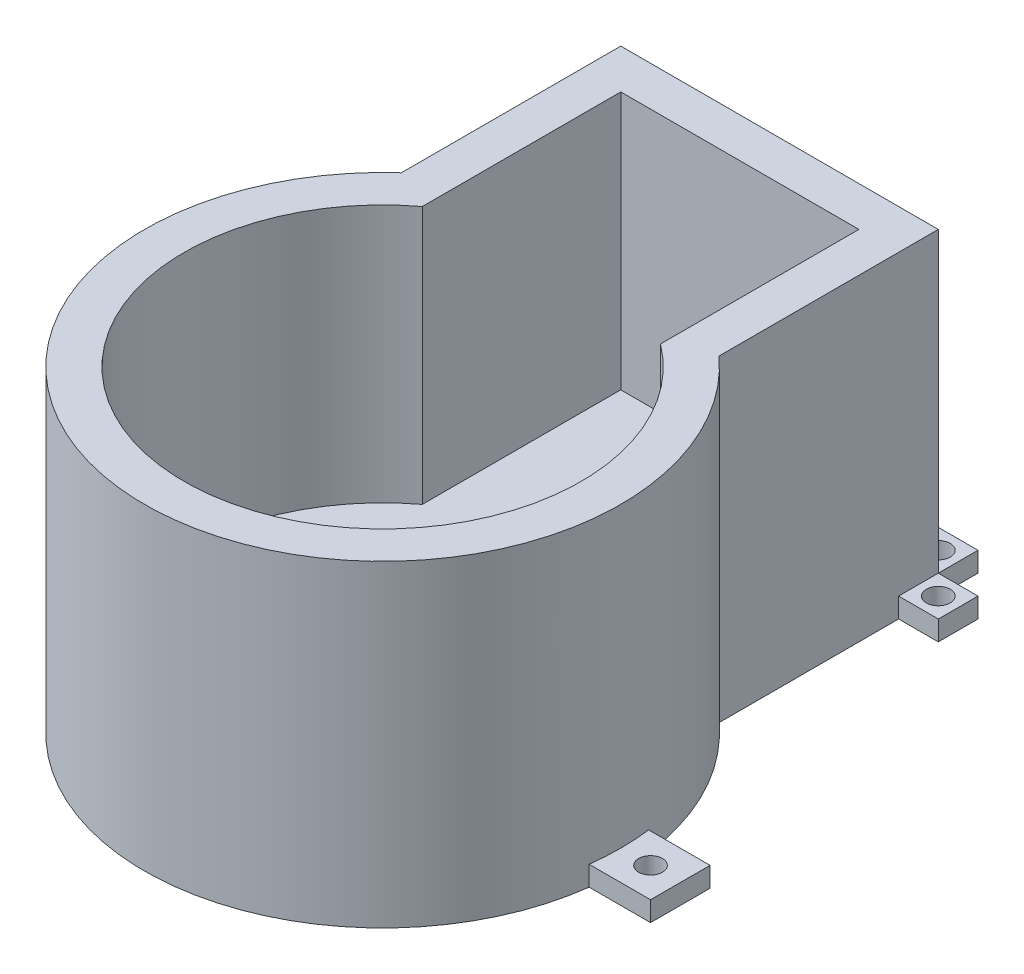
SolidWorks part; units mm, degrees
ref_plane "Front Plane" through (0, 0, 0) normal (0, 0, 1) x (1, 0, 0)
ref_plane "Top Plane" through (0, 0, 0) normal (0, 1, 0) x (1, 0, 0)
ref_plane "Right Plane" through (0, 0, 0) normal (1, 0, 0) x (0, 0, -1)
sketch "Sketch1" plane through (0, 0, 0) normal (0, 1, 0) x (1, 0, 0)
  line L0 (0, 40) -> (0, -40) construction
  line L1 (-40, 40) -> (40, 40)
  line L2 (-40, 40) -> (-40, -40)
  line L3 (-40, -40) -> (40, -40)
  line L4 (40, 40) -> (40, -40)
  line L5 (-40, 40) -> (40, -40) construction
  line L6 (-40, -40) -> (40, 40) construction
  circle A0 centre (0, -60) radius 60
  point P0 (0, 0)
  dimension "D4" = 120
  dimension "D1" = 80
  dimension "D2" = 80
  dimension "D3" = 60
extrude "Boss-Extrude1" add sketch "Sketch1" along normal blind 80
sketch "Sketch2" plane through (0, 80, 0) normal (0, 1, 0) x (1, 0, 0)
  line L1 (-30, 30) -> (30, 30)
  line L2 (-30, 30) -> (-30, -30)
  line L3 (-30, -30) -> (30, -30)
  line L4 (30, 30) -> (30, -30)
  line L5 (-30, 30) -> (30, -30) construction
  line L6 (-30, -30) -> (30, 30) construction
  circle A0 centre (0, -60) radius 50
  point P0 (0, 0)
  dimension "D3" = 100
  dimension "D1" = 60
  dimension "D2" = 60
extrude "Cut-Extrude1" cut sketch "Sketch2" against normal blind 65 contours A0 L4 L1 L2 | L4 A0 L2 L3 | L2 A0 L4 L3 region at (0, 80, -8.3069) region at (0, 80, 21.3384) region at (0, 80, 65.6974)
sketch "Sketch3" plane through (0, 0, 0) normal (0, -1, 0) x (1, 0, 0)
  line L0 (0, 120) -> (0, -40) construction
  line L1 (30, -30) -> (50, -30)
  line L2 (30, -30) -> (30, -50)
  line L3 (30, -50) -> (50, -50)
  line L4 (50, -30) -> (50, -50)
  line L5 (30, -30) -> (50, -50) construction
  line L6 (30, -50) -> (50, -30) construction
  line L7 (-40, -40) -> (40, -40) construction
  line L8 (-30, -50) -> (-50, -30) construction
  line L9 (50, -50) -> (40, -50)
  line L10 (50, -50) -> (50, -40)
  line L11 (50, -40) -> (40, -40)
  line L12 (40, -50) -> (40, -40)
  line L13 (-30, -30) -> (-50, -50) construction
  line L14 (-40, -50) -> (-40, -40)
  line L15 (-50, -40) -> (-40, -40)
  line L16 (-50, -50) -> (-50, -40)
  line L17 (-50, -50) -> (-40, -50)
  line L18 (-50, -30) -> (-50, -50)
  line L19 (-30, -50) -> (-50, -50)
  line L20 (-30, -30) -> (-30, -50)
  line L21 (-30, -30) -> (-50, -30)
  line L22 (-60, 60) -> (60, 60) construction
  line L23 (-60, 60) -> (-75, 60) construction
  line L24 (-75, 67.5) -> (75, 67.5)
  line L25 (-75, 67.5) -> (-75, 52.5)
  line L26 (-75, 52.5) -> (75, 52.5)
  line L27 (75, 67.5) -> (75, 52.5)
  line L28 (-75, 67.5) -> (75, 52.5) construction
  line L29 (-75, 52.5) -> (75, 67.5) construction
  arc A0 (40, 15.2786) -> (-40, 15.2786) centre (0, 60) ccw construction
  circle A1 centre (45, -35) radius 3
  circle A2 centre (35, -45) radius 3
  circle A3 centre (-35, -45) radius 3
  circle A4 centre (-45, -35) radius 3
  circle A6 centre (-67.5, 60) radius 3
  circle A7 centre (67.5, 60) radius 3
  point P0 (40, -40)
  point P31 (-40, -40)
  point P35 (0, 60)
  arc M17 (40, 15.2786) -> (-40, 15.2786) centre (0, 60) ccw
  line M18 (-40, 15.2786) -> (-40, -40)
  line M19 (-40, -40) -> (40, -40)
  line M20 (40, -40) -> (40, 15.2786)
  dimension "D3" = 6
  dimension "D4" = 6
  dimension "D11" = 6
  dimension "D1" = 20
  dimension "D2" = 20
  dimension "D5" = 5
  dimension "D6" = 5
  dimension "D7" = 5
  dimension "D8" = 5
  dimension "D9" = 15
  dimension "D10" = 150
extrude "Boss-Extrude2" add sketch "Sketch3" against normal blind 5 contours L25 L26 L24 A6 M17 | L27 L24 L26 A7 M17 | L21 L18 L15 A4 M18 | L20 L14 L19 A3 M19 | L3 L12 L2 A2 M19 | L11 L4 L1 A1 M20 region at (45, 0, -30.1414) region at (35, 0, -40.1414) region at (-30.1414, 0, -45) region at (60.2155, 0, 60) region at (-45, 0, -39.8586) region at (-67.2647, 0, 52.7155)
